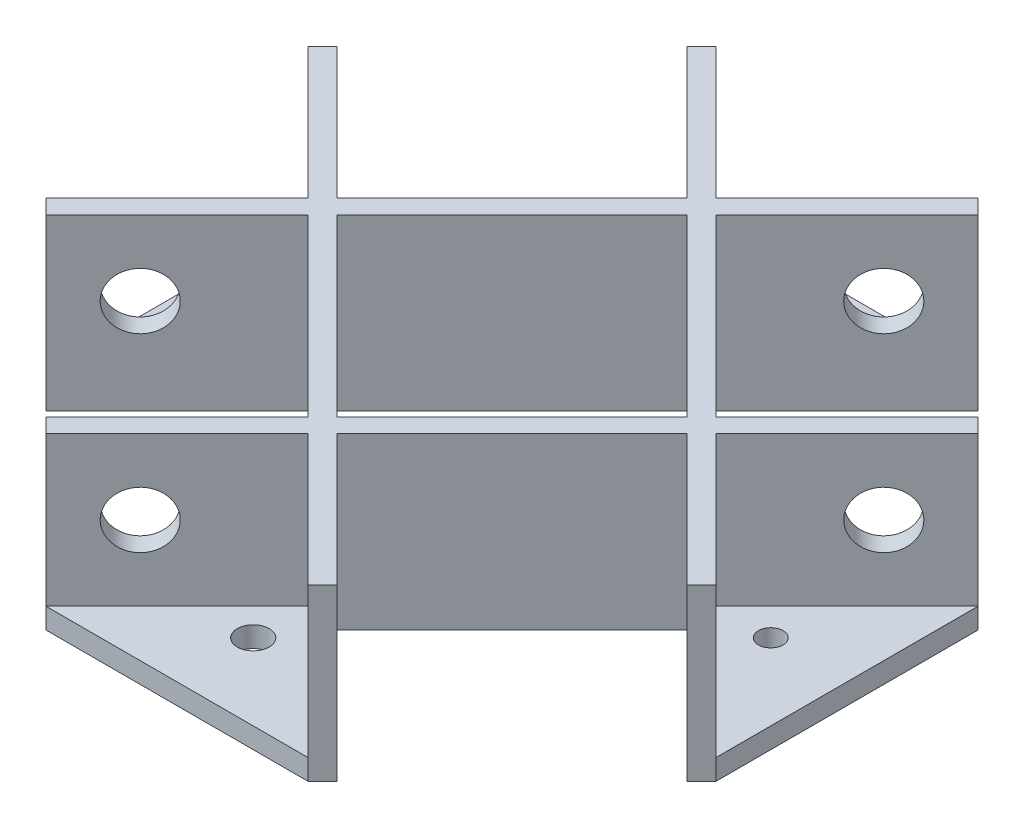
SolidWorks part; units mm, degrees
material "Windform GT"
ref_plane "Front Plane" through (0, 0, 0) normal (0, 0, 1) x (1, 0, 0)
ref_plane "Top Plane" through (0, 0, 0) normal (0, 1, 0) x (1, 0, 0)
ref_plane "Right Plane" through (0, 0, 0) normal (1, 0, 0) x (0, 0, -1)
ref_axis "Axis1" through (0, 2.1, 0) along (0, -1, 0)
sketch "Usable Space" plane through (0, 0, 0) normal (0, 1, 0) x (1, 0, 0)
  line L1 (-32.5, -32.5) -> (32.5, -32.5) construction
  line L2 (-32.5, -32.5) -> (-32.5, 32.5) construction
  line L3 (-32.5, 32.5) -> (32.5, 32.5) construction
  line L4 (32.5, -32.5) -> (32.5, 32.5) construction
  line L5 (-32.5, -32.5) -> (32.5, 32.5) construction
  line L6 (-32.5, 32.5) -> (32.5, -32.5) construction
  point P0 (0, 0)
  dimension "D1" = 65
sketch "Sketch3" plane through (0, 0, 0) normal (0, 1, 0) x (1, 0, 0)
  line L0 (-32.5, -12.701) -> (-12.701, -32.5)
  line L1 (-32.5, -32.5) -> (-32.5, 32.5) construction
  line L2 (-12.701, -32.5) -> (0, -19.799)
  line L3 (-32.5, -32.5) -> (32.5, 32.5) construction
  line L4 (0, -19.799) -> (0, 0)
  line L5 (0, 0) -> (-19.799, 0)
  line L7 (-19.799, 0) -> (-32.5, -12.701)
  line L8 (-32.5, -32.5) -> (32.5, -32.5) construction
  dimension "D1" = 28
extrude "General shape" add sketch "Sketch3" along normal blind 2
sketch "Sketch4" plane through (0, 2, 0) normal (0, 1, 0) x (1, 0, 0)
  line L0 (-19.799, 0) -> (-32.5, -12.701)
  line L1 (-19.799, 0) -> (-32.5, -12.701) construction
  line L2 (-32.5, -12.701) -> (-31.0858, -14.1152)
  line L3 (-31.0858, -14.1152) -> (-16.9706, 0)
  line L4 (0, 0) -> (-19.799, 0) construction
  line L5 (-16.9706, 0) -> (-19.799, 0)
  line L6 (-22.6005, -22.6005) -> (0, 0) construction
  line L7 (-32.5, -12.701) -> (-12.701, -32.5) construction
  line L8 (-14.1152, -31.0858) -> (0, -16.9706)
  line L9 (-12.701, -32.5) -> (-14.1152, -31.0858)
  line L10 (0, -19.799) -> (-12.701, -32.5)
  line L11 (0, -16.9706) -> (0, -19.799)
  dimension "D1" = 2
extrude "Retaining walls" add sketch "Sketch4" along normal blind 14.5
sketch "Sketch14" plane through (0, 0, 0) normal (0, -1, 0) x (1, 0, 0)
  line L0 (-19.799, 0) -> (-32.5, 12.701)
  line L1 (-19.799, 0) -> (-32.5, 12.701) construction
  line L2 (-32.5, 12.701) -> (-32.5, 0)
  line L3 (-32.5, 0) -> (-19.799, 0)
  line L4 (0, 19.799) -> (0, 32.5)
  line L5 (0, 32.5) -> (-12.701, 32.5)
  line L6 (-12.701, 32.5) -> (0, 19.799) construction
  line L7 (0, 19.799) -> (-12.701, 32.5)
  circle A1 centre (-29.049, 0) radius 1 construction
  dimension "D1" = 9.25
  dimension "D2" = 2
extrude "Exterior mounting edge" add sketch "Sketch14" against normal blind 2
sketch "Sketch18" plane through (0, 2, 0) normal (0, 1, 0) x (1, 0, 0)
  line L0 (-16.9706, 0) -> (0, -16.9706)
  line L1 (-18.3848, -1.4142) -> (-1.4142, -18.3848)
  line L2 (-31.0858, -14.1152) -> (-16.9706, 0) construction
  line L3 (0, -16.9706) -> (-14.1152, -31.0858) construction
  line L4 (-18.3848, -1.4142) -> (-16.9706, 0)
  line L5 (0, -16.9706) -> (-1.4142, -18.3848)
  dimension "D1" = 2
extrude "Rear wall" add sketch "Sketch18" along normal blind 14.5
sketch "Sketch19" plane through (-8.4853, 0, 8.4853) normal (0.7071, 0, -0.7071) x (-0.7071, 0, -0.7071)
  line L0 (0, 16.5) -> (0, 2) construction
  line L1 (-12, 16.5) -> (12, 16.5) construction
  line L2 (-12, 2) -> (12, 2) construction
  point P6 (0, 9.25)
fillet "Fillet13" [suppressed] radius 1
ref_plane "Plane2" [suppressed] through (0, 0, 0) normal (0.7071, 0, 0.7071) x (0.7071, 0, -0.7071)
sketch "Sketch35" plane through (-9.8995, 0, -9.8995) normal (-0.7071, 0, -0.7071) x (-0.7071, 0, 0.7071)
  line L0 (25.5, 16.5) -> (25.5, 2) construction
  line L2 (14, 16.5) -> (14, 2) construction
  line L3 (14, 2) -> (31.9619, 2) construction
  line L5 (14, 16.5) -> (31.9619, 16.5) construction
  circle A0 centre (25.5, 9.25) radius 2.75
  point P2 (0, 0)
  point P3 (0, 0)
  dimension "D1" = 5.5
  dimension "D2" = 11.5
extrude "Cut-Extrude2" cut sketch "Sketch35" against normal through all both and the other way through all
pattern_circular "CirPattern2" count 4 over 360 about axis through (0, 2.1, 0) along (0, -1, 0) of "General shape", "Retaining walls"
combine bodies "Combine1" operation type add bodies to combine 104 111 110 139
sketch "Exterior mounting hole location" plane through (0, 2, 0) normal (0, 1, 0) x (1, 0, 0)
  line L0 (-32.5, 0) -> (-19.799, 0) construction
  line L1 (-32.5, -12.701) -> (-32.5, 12.701) construction
  point P5 (-25.1, 0)
  point P7 (0, 25.1)
  point P13 (25.1, 0)
  point P14 (0, -25.1)
  dimension "D1" = 4
  dimension "D2" = 25.1
hole_wizard "Exterior mounting hole" positions "Sketch16" profile "Sketch17" hole size "M2" standard "ANSI Metric" end condition up to next
sketch "Sketch16" plane through (0, 2, 0) normal (0, 1, 0) x (1, 0, 0)
  point P0 (-25.1, 0)
  point P15 (25.1, 0)
sketch "Sketch17" plane through (-25.1, 2, 0) normal (1, 0, 0) x (0, 0, 1)
  line L0 (0, 0) -> (0, 2)
  line L1 (0, 2) -> (1.2, 2)
  line L2 (1.2, 2) -> (1.2, 0)
  line L5 (1.2, 0) -> (0, 0)
  line L11 (0, -6.35) -> (0, 107.95) construction
  dimension "Thru Hole Dia." = 2.4
  dimension "Thru Hole Depth" = 2
hole_wizard "Shoulder screw mounting holes " positions "Sketch24" profile "Sketch25" hole size "M2.5" standard "ANSI Metric" end condition up to next
sketch "Sketch24" plane through (0, 2, 0) normal (0, 1, 0) x (1, 0, 0)
  point P0 (0, -25.1)
  point P3 (0, 25.1)
sketch "Sketch25" plane through (0, 2, 25.1) normal (1, 0, 0) x (0, 0, 1)
  line L0 (0, 0) -> (0, 2)
  line L1 (0, 2) -> (1.55, 2)
  line L2 (1.55, 2) -> (1.55, 0)
  line L5 (1.55, 0) -> (0, 0)
  line L11 (0, -6.35) -> (0, 107.95) construction
  dimension "Thru Hole Dia." = 3.1
  dimension "Thru Hole Depth" = 2
sketch "Sketch23" plane through (0, 2, 0) normal (0, 1, 0) x (1, 0, 0)
  line L0 (0, 16.9706) -> (-16.9706, 0)
  line L5 (-16.9706, 0) -> (0, -16.9706)
  line L6 (0, -16.9706) -> (16.9706, 0)
  line L7 (16.9706, 0) -> (0, 16.9706)
  line L8 (31.0858, 14.1152) -> (18.3848, 1.4142) construction
  line L9 (18.3848, 1.4142) -> (1.4142, 18.3848) construction
  line L10 (1.4142, 18.3848) -> (14.1152, 31.0858) construction
  line L11 (-18.3848, 1.4142) -> (-31.0858, 14.1152) construction
  line L12 (-1.4142, 18.3848) -> (-18.3848, 1.4142) construction
  line L13 (-14.1152, 31.0858) -> (-1.4142, 18.3848) construction
  line L14 (-1.4142, -18.3848) -> (-14.1152, -31.0858) construction
  line L15 (-18.3848, -1.4142) -> (-1.4142, -18.3848) construction
  line L16 (-31.0858, -14.1152) -> (-18.3848, -1.4142) construction
  line L17 (14.1152, -31.0858) -> (1.4142, -18.3848) construction
  line L18 (18.3848, -1.4142) -> (31.0858, -14.1152) construction
  line L19 (1.4142, -18.3848) -> (18.3848, -1.4142) construction
  line L20 (31.0858, 14.1152) -> (18.3848, 1.4142)
  line L21 (18.3848, 1.4142) -> (1.4142, 18.3848)
  line L22 (1.4142, 18.3848) -> (14.1152, 31.0858)
  line L23 (-18.3848, 1.4142) -> (-31.0858, 14.1152)
  line L24 (-1.4142, 18.3848) -> (-18.3848, 1.4142)
  line L25 (-14.1152, 31.0858) -> (-1.4142, 18.3848)
  line L26 (-1.4142, -18.3848) -> (-14.1152, -31.0858)
  line L27 (-18.3848, -1.4142) -> (-1.4142, -18.3848)
  line L28 (-31.0858, -14.1152) -> (-18.3848, -1.4142)
  line L29 (14.1152, -31.0858) -> (1.4142, -18.3848)
  line L30 (18.3848, -1.4142) -> (31.0858, -14.1152)
  line L31 (1.4142, -18.3848) -> (18.3848, -1.4142)
  line L32 (-14.1152, 31.0858) -> (-31.0858, 14.1152)
  line L33 (-14.1152, -31.0858) -> (-31.0858, -14.1152)
  line L34 (14.1152, -31.0858) -> (31.0858, -14.1152)
  line L35 (31.0858, 14.1152) -> (14.1152, 31.0858)
extrude "Cut-Extrude1" cut sketch "Sketch23" against normal up to next
